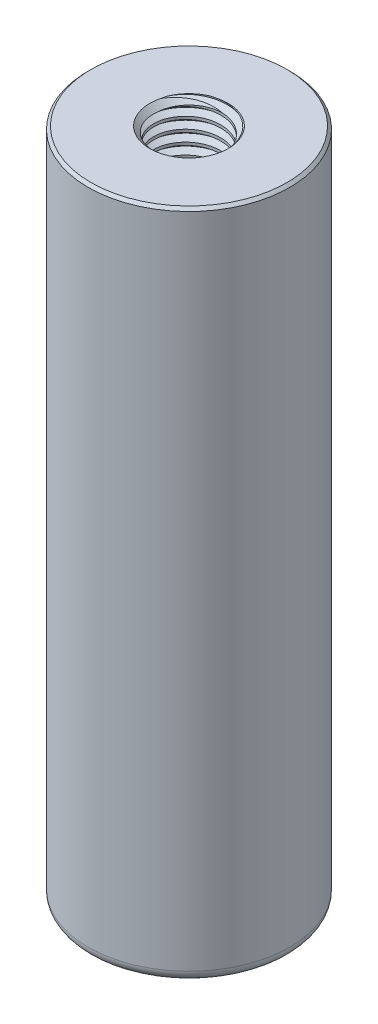
SolidWorks part; units mm, degrees
ref_plane "Front Plane" through (0, 0, 0) normal (0, 0, 1) x (1, 0, 0)
ref_plane "Top Plane" through (0, 0, 0) normal (0, 1, 0) x (1, 0, 0)
ref_plane "Right Plane" through (0, 0, 0) normal (1, 0, 0) x (0, 0, -1)
sketch "Sketch1" plane through (0, 0, 0) normal (0, 1, 0) x (1, 0, 0)
  circle A0 centre (0, 0) radius 9
  dimension "D1" = 18
extrude "Boss-Extrude1" add sketch "Sketch1" against normal blind 60
sketch "Sketch2" plane through (0, 0, 0) normal (0, 1, 0) x (1, 0, 0)
  circle A0 centre (0, 0) radius 3
  dimension "D1" = 6
extrude "Cut-Extrude1" cut sketch "Sketch2" against normal blind 10
sketch "Sketch7" plane through (0, -60, 0) normal (0, -1, 0) x (1, 0, 0)
  circle A1 centre (0, 0) radius 7
  dimension "D1" = 14
extrude "Cut-Extrude2" cut sketch "Sketch7" against normal blind 50
chamfer "Chamfer1" distance 0.25 angle 45 1 edges at (0, 0, 9)
chamfer "Chamfer2" distance 0.5 angle 45 1 edges at (0, 0, 3)
thread "Thread2" pitch 1 method cut profile "Thread Profile3" start angle 0, offset 2, length 12, pitch 1, diameter 6
ref_plane "Plane3" through (-3, 1.5, 0) normal (0, 0, 1) x (-1, 0, 0)
sketch "Thread Profile3" plane through (-3, 1.5, 0) normal (0, 0, 1) x (-1, 0, 0)
  line L0 (0, 0) -> (0, 1) construction
  line L1 (0, 0) -> (0.5413, 0.3125)
  line L2 (0.5413, 0.3125) -> (0.5413, 0.4375)
  line L3 (0.5413, 0.4375) -> (0, 0.75)
  line L4 (0.5413, 0.375) -> (0, 0.375) construction
  line L11 (0, 0) -> (0, 0.75)
  point P2 (0, 0)
  dimension "Pitch" = 1
  dimension "Profile_Angle" = 60
  dimension "Profile_Land" = 0.125
  dimension "Profile_Height" = 0.5413
chamfer "Chamfer3" distance 1 angle 45 2 edges at (0, -60, -7) (0, -10, -7)
fillet "Fillet1" radius 1 1 edges at (0, -60, 9)
